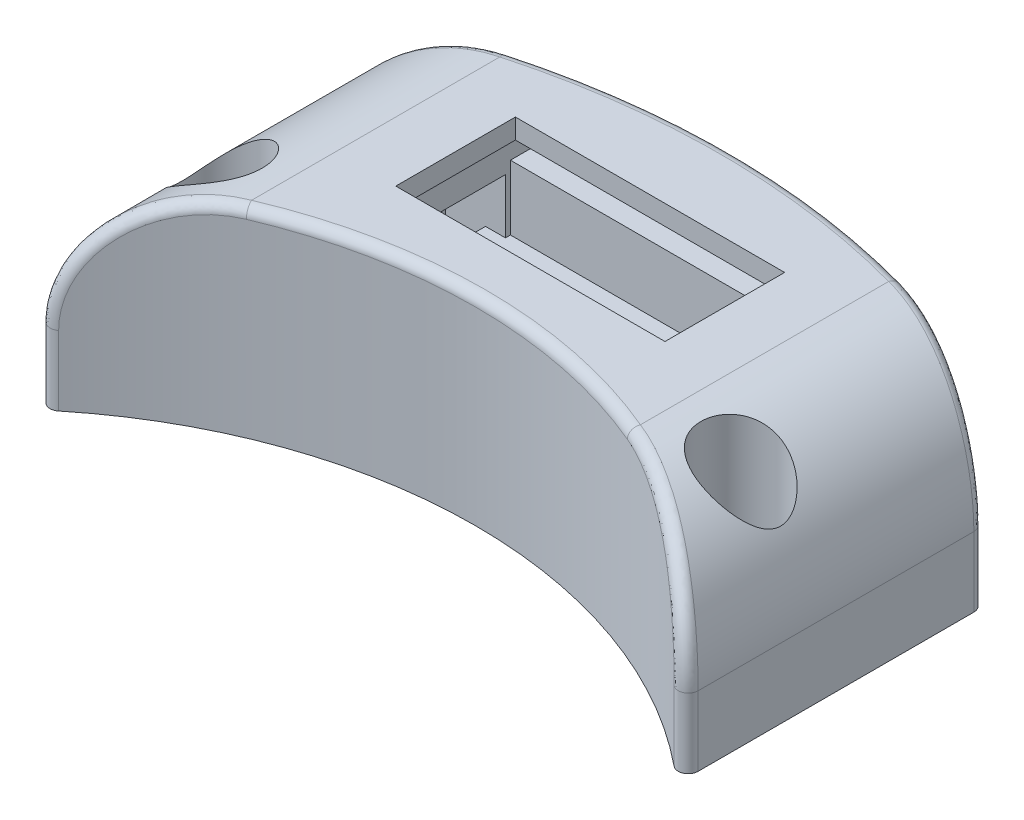
SolidWorks part; units mm, degrees
ref_plane "Front Plane" through (0, 0, 0) normal (0, 0, 1) x (1, 0, 0)
ref_plane "Top Plane" through (0, 0, 0) normal (0, 1, 0) x (1, 0, 0)
ref_plane "Right Plane" through (0, 0, 0) normal (1, 0, 0) x (0, 0, -1)
sketch "Sketch1" plane through (0, 0, 0) normal (0, 1, 0) x (1, 0, 0)
  line L0 (-32.5, 49) -> (32.5, 49) construction
  line L1 (-32.5, 67.112) -> (-32.5, 36.6708)
  line L2 (15, 71) -> (15.4134, 72.9568) construction
  line L3 (32.5, 36.6708) -> (32.5, 67.112)
  line L4 (-15, 50) -> (15, 50)
  line L5 (-15, 50) -> (-15, 71)
  line L6 (-15, 71) -> (15, 71)
  line L7 (15, 50) -> (15, 71)
  line L8 (-15, 50) -> (15, 71) construction
  line L9 (-15, 71) -> (15, 50) construction
  arc A0 (32.5, 36.6708) -> (-32.5, 36.6708) centre (0, 0) ccw
  arc A1 (32.5, 67.112) -> (-32.5, 67.112) centre (0, 0) ccw
  point P1 (0, 60.5)
  point P7 (0, 49)
  dimension "D1" = 2
  dimension "D2" = 98
  dimension "D3" = 65
  dimension "D4" = 30
  dimension "D5" = 21
  dimension "D6" = 1
extrude "Boss-Extrude1" add sketch "Sketch1" along normal blind 20
sketch "Sketch4" plane through (0, 20, 0) normal (0, 1, 0) x (1, 0, 0)
  line L1 (-15, 71) -> (15, 71)
  line L2 (-15, 71) -> (-15, 50)
  line L3 (-15, 50) -> (15, 50)
  line L4 (15, 71) -> (15, 50)
  line L5 (-15, 71) -> (15, 50) construction
  line L6 (-15, 50) -> (15, 71) construction
  line L7 (-13.5, 54.5) -> (13.5, 54.5)
  line L8 (-13.5, 54.5) -> (-13.5, 66.5)
  line L9 (-13.5, 66.5) -> (13.5, 66.5)
  line L10 (13.5, 54.5) -> (13.5, 66.5)
  line L11 (-13.5, 54.5) -> (13.5, 66.5) construction
  line L12 (-13.5, 66.5) -> (13.5, 54.5) construction
  point P4 (0, 60.5)
  point P7 (0, 60.5)
  dimension "D1" = 27
  dimension "D2" = 12
extrude "Boss-Extrude2" add sketch "Sketch4" against normal blind 2
sketch "Sketch7" plane through (0, 0, 0) normal (0, -1, 0) x (1, 0, 0)
  line L0 (-26, -49.5984) -> (26, -49.5984) construction
  circle A0 centre (-26, -49.5984) radius 2
  circle A1 centre (26, -49.5984) radius 2
  circle A3 centre (0, 0) radius 56 construction
  point P4 (0, -49.5984)
  dimension "D1" = 4
  dimension "D2" = 4
  dimension "D4" = 112
  dimension "D3" = 52
extrude "Cut-Extrude4" cut sketch "Sketch7" against normal through all both and the other way through all
sketch "Sketch8" plane through (0, 20, 0) normal (0, 1, 0) x (1, 0, 0)
  circle A0 centre (-26, 49.5984) radius 4
  circle A1 centre (26, 49.5984) radius 4
  dimension "D1" = 8
  dimension "D2" = 8
extrude "Cut-Extrude5" cut sketch "Sketch8" against normal offset from surface (17 mm away) 3 up to face at (-26, 0, -47.5984)
fillet "Fillet1" radius 13 2 edges at (32.5, 20, -51.8914) (-32.5, 20, -51.8914)
fillet "Fillet2" radius 1 10 edges at (-32.5, 3.5, -36.6708) (-28.1766, 16.6807, -40.0884) (32.5, 3.5, -36.6708) (30.5905, 13.7824, -38.2782) (32.5, 3.5, -67.112) (27.8741, 16.9436, -69.1614) (-32.5, 3.5, -67.112) (-30.0628, 14.5781, -68.2385) (0, 20, -49) (0, 20, -74.5672)
sketch "Sketch9" plane through (0, 0, 0) normal (0, -1, 0) x (1, 0, 0)
  line L1 (-21, -67) -> (21, -67)
  line L2 (-21, -67) -> (-21, -54)
  line L3 (-21, -54) -> (21, -54)
  line L4 (21, -67) -> (21, -54)
  line L5 (-21, -67) -> (21, -54) construction
  line L6 (-21, -54) -> (21, -67) construction
  point P4 (0, -60.5)
  dimension "D1" = 13
  dimension "D2" = 42
extrude "Cut-Extrude6" cut sketch "Sketch9" against normal offset from surface (14 mm away) 4 up to face at (0, 18, -60.5)
sketch "Sketch10" plane through (0, 0, 0) normal (0, -1, 0) x (1, 0, 0)
  line L0 (15, -50) -> (15, -71) construction
  line L1 (14.5, -70.5) -> (-14.5, -70.5)
  line L2 (14.5, -70.5) -> (14.5, -67)
  line L3 (14.5, -67) -> (-14.5, -67)
  line L4 (-14.5, -70.5) -> (-14.5, -67)
  line L5 (14.5, -70.5) -> (-14.5, -67) construction
  line L6 (14.5, -67) -> (-14.5, -70.5) construction
  line L7 (-14.5, -50.5) -> (14.5, -50.5)
  line L8 (-14.5, -50.5) -> (-14.5, -54)
  line L9 (-14.5, -54) -> (14.5, -54)
  line L10 (14.5, -50.5) -> (14.5, -54)
  line L11 (-14.5, -50.5) -> (14.5, -54) construction
  line L12 (-14.5, -54) -> (14.5, -50.5) construction
  line L13 (-15, -71) -> (15, -71) construction
  line L14 (-15, -50) -> (-15, -71) construction
  line L15 (-15, -50) -> (15, -50) construction
  line L16 (13.5, -66.5) -> (-13.5, -66.5) construction
  line L17 (-13.5, -54.5) -> (13.5, -54.5) construction
  point P4 (0, -68.75)
  point P9 (0, -52.25)
  dimension "D1" = 0.5
  dimension "D2" = 0.5
  dimension "D3" = 0.5
  dimension "D4" = 0.5
  dimension "D5" = 0.5
  dimension "D6" = 0.5
  dimension "D7" = 0.5
  dimension "D8" = 0.5
extrude "Boss-Extrude3" add sketch "Sketch10" against normal offset from surface (15.5 mm away) 2.5 separate body up to face at (0, 18, -60.5)
sketch "Sketch11" plane through (0, 0, 0) normal (0, -1, 0) x (1, 0, 0)
  line L20 (-20.5, -66.5) -> (-14.5, -66.5)
  line L21 (20.5, -66.5) -> (20.5, -54.5)
  line L22 (20.5, -54.5) -> (14.5, -54.5)
  line L23 (-20.5, -54.5) -> (-20.5, -66.5)
  line L24 (15, -67) -> (21, -67) construction
  line L25 (21, -67) -> (21, -54) construction
  line L26 (-21, -54) -> (-21, -67) construction
  line L27 (-15, -54) -> (-21, -54) construction
  line L28 (-14.5, -54.5) -> (-20.5, -54.5)
  line L29 (14.5, -67) -> (-14.5, -67)
  line L30 (14.5, -67) -> (14.5, -66.5)
  line L31 (14.5, -54) -> (-14.5, -54)
  line L32 (-14.5, -67) -> (-14.5, -66.5)
  line L33 (14.5, -67) -> (-14.5, -54) construction
  line L34 (14.5, -54) -> (-14.5, -67) construction
  line L35 (14.5, -66.5) -> (20.5, -66.5)
  line L36 (-14.5, -54.5) -> (-14.5, -54)
  line L37 (14.5, -54.5) -> (14.5, -54)
  point P15 (0, -60.5)
  dimension "D1" = 0.5
  dimension "D2" = 0.5
  dimension "D3" = 0.5
  dimension "D4" = 0.5
extrude "Boss-Extrude4" add sketch "Sketch11" against normal offset from surface (9 mm away) 5 up to face at (18, 14, -60.5)
sketch "Sketch12" plane through (0, 9, 0) normal (0, 1, 0) x (1, 0, 0)
  line L0 (-14.5, 54.5) -> (-20.5, 54.5) construction
  line L1 (-20.5, 54.5) -> (-16.5, 54.5)
  line L2 (-20.5, 54.5) -> (-20.5, 66.5)
  line L3 (-20.5, 66.5) -> (-16.5, 66.5)
  line L4 (-16.5, 54.5) -> (-16.5, 66.5)
  line L5 (-20.5, 54.5) -> (-16.5, 66.5) construction
  line L6 (-20.5, 66.5) -> (-16.5, 54.5) construction
  line L7 (-20.5, 54.5) -> (-20.5, 66.5) construction
  line L8 (-20.5, 66.5) -> (-14.5, 66.5) construction
  point P4 (-18.5, 60.5)
  dimension "D1" = 4
extrude "Cut-Extrude7" cut sketch "Sketch12" against normal offset from surface (7 mm away) 2 up to face at (0, 0, -60.5)
sketch "Sketch18" plane through (-16.5, 0, 0) normal (-1, 0, 0) x (0, 0, 1)
  line L0 (-63.5, 9) -> (-57.5, 9)
  line L1 (-54.5, 9) -> (-66.5, 9) construction
  line L4 (-63.5, 9) -> (-63.5, 3)
  line L5 (-63.5, 3) -> (-57.5, 3)
  line L6 (-57.5, 3) -> (-57.5, 9)
  point P5 (-60.5, 9)
  dimension "D1" = 6
  dimension "D2" = 6
extrude "Cut-Extrude8" cut sketch "Sketch18" against normal offset from surface (21.5 mm away) 5 up to plane "Right Plane" offset beyond the face yes
sketch "Sketch24" plane through (0, 0, 0) normal (1, 0, 0) x (0, 0, -1)
  line L0 (49, 0) -> (56, 0)
  line L1 (56, 0) -> (60.5, 3)
  line L2 (60.5, 3) -> (57.5, 9)
  line L3 (57.5, 9) -> (49, 0)
  line L4 (66.5, 9) -> (54.5, 9) construction
  line L5 (57.5, 3) -> (57.5, 9) construction
  line L6 (50, 0) -> (71, 0) construction
  line L8 (63.5, 3) -> (57.5, 3) construction
  point P23 (60.5, 3)
  dimension "D1" = 7
extrude "Cut-Extrude10" cut sketch "Sketch24" against normal mid plane 10
